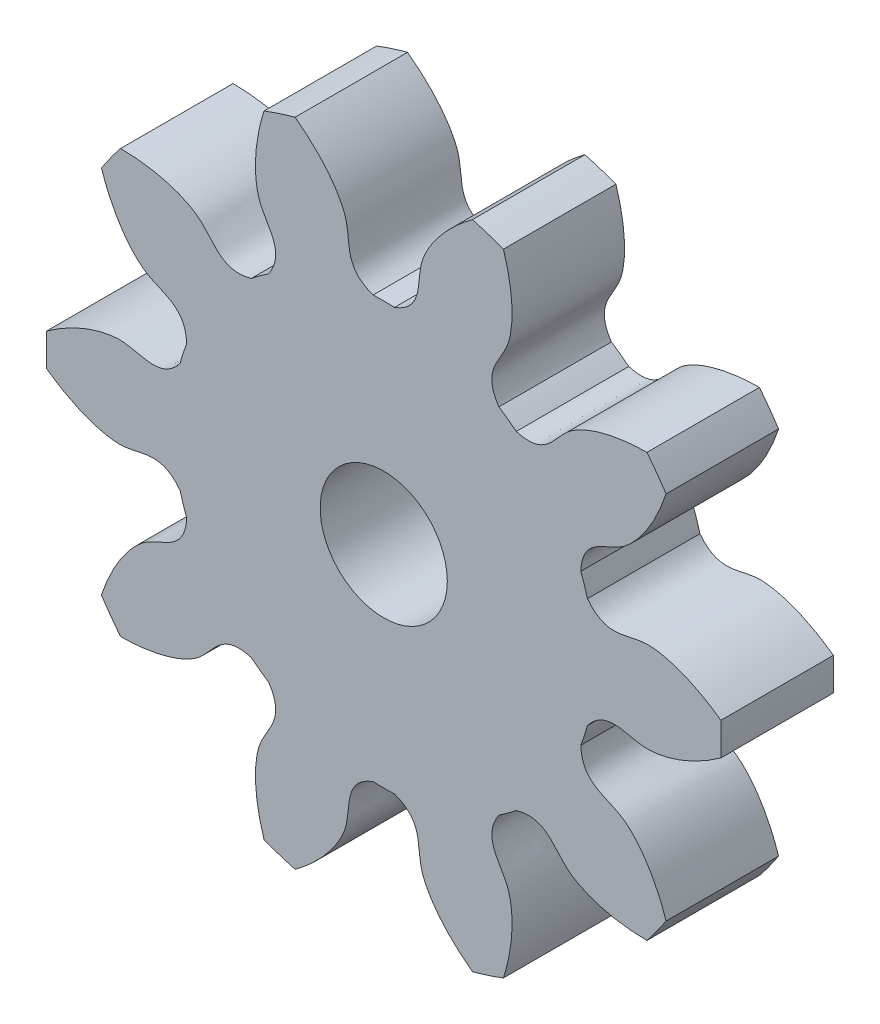
SolidWorks part; units mm, degrees
material "尼龙 6/10"
ref_plane "前视基准面" through (0, 0, 0) normal (0, 0, 1) x (1, 0, 0)
ref_plane "上视基准面" through (0, 0, 0) normal (0, 1, 0) x (1, 0, 0)
ref_plane "右视基准面" through (0, 0, 0) normal (1, 0, 0) x (0, 0, -1)
sketch "草图1" plane through (0, 0, 0) normal (0, 0, 1) x (1, 0, 0)
  circle A0 centre (0, 0) radius 3
extrude "凸台-拉伸1" add sketch "草图1" along normal blind 1
ref_axis "基准轴1" through (0, 0, -1.5) along (0, 0, 1)
sketch "草图2" plane through (0, 0, 0) normal (0, 0, 1) x (1, 0, 0)
  line L0 (0, 0) -> (0, 3) construction
  circle A0 centre (0, 0) radius 3 construction
  arc A1 (0.0952, 1.8726) -> (-0.0952, 1.8726) centre (0, 0) ccw
  arc A2 (2.1268, 3.3471) -> (-2.1268, 3.3471) centre (0, 0) ccw
  spline S0 degree 3 poles (0.0952, 1.8726) (0.3627, 1.9703) (0.2869, 2.1853) (0.3443, 2.3623) (0.3473, 2.3708) (0.3507, 2.38) (0.3546, 2.3901) (0.3591, 2.4009) (0.3642, 2.4126) (0.3699, 2.4249) (0.3763, 2.438) (0.3834, 2.4518) (0.3911, 2.4663) (0.3997, 2.4815) (0.409, 2.4972) (0.4191, 2.5136) (0.4301, 2.5306) (0.4419, 2.5481) (0.4546, 2.5662) (0.4682, 2.5848) (0.4828, 2.6038) (0.4983, 2.6233) (0.5148, 2.6432) (0.5323, 2.6634) (0.5509, 2.684) (0.5705, 2.7049) (0.5911, 2.7261) (0.6129, 2.7476) (0.6358, 2.7692) (0.6598, 2.791) (0.6849, 2.8129) (0.7112, 2.835) (0.7386, 2.8571) (0.7672, 2.8792) (0.7971, 2.9013) (0.8281, 2.9234) (0.8603, 2.9453) (0.8938, 2.9671) (0.9285, 2.9888) (0.9644, 3.0102) (1.0015, 3.0314) (1.0399, 3.0522) (1.0796, 3.0728) (1.1204, 3.0929) (1.1626, 3.1126) (1.2059, 3.1319) (1.2506, 3.1506) (1.2964, 3.1688) (1.3435, 3.1864) (1.3918, 3.2034) (1.4414, 3.2197) (1.4921, 3.2353) (1.5441, 3.2501) (1.5972, 3.2642) (1.6516, 3.2773) (1.7071, 3.2896) (1.7638, 3.301) (1.8216, 3.3114) (1.8805, 3.3208) (1.9405, 3.3291) (2.0227, 3.3388) (2.0849, 3.3443) (2.1268, 3.3471) knots 0 0 0 0 0.201721 0.204697 0.208023 0.211699 0.215726 0.220102 0.224829 0.229906 0.235332 0.241109 0.247237 0.253714 0.260541 0.267719 0.275246 0.283124 0.291352 0.29993 0.308858 0.318136 0.327765 0.337743 0.348072 0.358751 0.36978 0.381158 0.392888 0.404967 0.417396 0.430176 0.443305 0.456785 0.470615 0.484795 0.499325 0.514205 0.529435 0.545016 0.560946 0.577227 0.593858 0.610839 0.62817 0.645851 0.663882 0.682264 0.700995 0.720077 0.739509 0.759291 0.779423 0.799905 0.820737 0.84192 0.863452 0.885335 0.907568 0.930151 0.953084 1 1 1 1
  spline S1 degree 3 poles (-0.0952, 1.8726) (-0.3627, 1.9703) (-0.2869, 2.1853) (-0.3443, 2.3623) (-0.3473, 2.3708) (-0.3507, 2.38) (-0.3546, 2.3901) (-0.3591, 2.4009) (-0.3642, 2.4126) (-0.3699, 2.4249) (-0.3763, 2.438) (-0.3834, 2.4518) (-0.3911, 2.4663) (-0.3997, 2.4815) (-0.409, 2.4972) (-0.4191, 2.5136) (-0.4301, 2.5306) (-0.4419, 2.5481) (-0.4546, 2.5662) (-0.4682, 2.5848) (-0.4828, 2.6038) (-0.4983, 2.6233) (-0.5148, 2.6432) (-0.5323, 2.6634) (-0.5509, 2.684) (-0.5705, 2.7049) (-0.5911, 2.7261) (-0.6129, 2.7476) (-0.6358, 2.7692) (-0.6598, 2.791) (-0.6849, 2.8129) (-0.7112, 2.835) (-0.7386, 2.8571) (-0.7672, 2.8792) (-0.7971, 2.9013) (-0.8281, 2.9234) (-0.8603, 2.9453) (-0.8938, 2.9671) (-0.9285, 2.9888) (-0.9644, 3.0102) (-1.0015, 3.0314) (-1.0399, 3.0522) (-1.0796, 3.0728) (-1.1204, 3.0929) (-1.1626, 3.1126) (-1.2059, 3.1319) (-1.2506, 3.1506) (-1.2964, 3.1688) (-1.3435, 3.1864) (-1.3918, 3.2034) (-1.4414, 3.2197) (-1.4921, 3.2353) (-1.5441, 3.2501) (-1.5972, 3.2642) (-1.6516, 3.2773) (-1.7071, 3.2896) (-1.7638, 3.301) (-1.8216, 3.3114) (-1.8805, 3.3208) (-1.9405, 3.3291) (-2.0227, 3.3388) (-2.0849, 3.3443) (-2.1268, 3.3471) knots 0 0 0 0 0.201721 0.204697 0.208023 0.211699 0.215726 0.220102 0.224829 0.229906 0.235332 0.241109 0.247237 0.253714 0.260541 0.267719 0.275246 0.283124 0.291352 0.29993 0.308858 0.318136 0.327765 0.337743 0.348072 0.358751 0.36978 0.381158 0.392888 0.404967 0.417396 0.430176 0.443305 0.456785 0.470615 0.484795 0.499325 0.514205 0.529435 0.545016 0.560946 0.577227 0.593858 0.610839 0.62817 0.645851 0.663882 0.682264 0.700995 0.720077 0.739509 0.759291 0.779423 0.799905 0.820737 0.84192 0.863452 0.885335 0.907568 0.930151 0.953084 1 1 1 1
extrude "切除-拉伸1" cut sketch "草图2" along normal through all
pattern_circular "阵列(圆周)1" count 10 every 36 about axis through (0, 0, -1.5) along (0, 0, 1) of "切除-拉伸1"
sketch "草图3" [suppressed] plane through (0, 0, 0) normal (0, 0, 1) x (1, 0, 0)
  circle A0 centre (0, 0) radius 2.5 construction
  dimension "Dn" = 5
sketch "草图4" plane through (0, 0, 1) normal (0, 0, 1) x (1, 0, 0)
  circle A0 centre (0, 0) radius 0.565
  dimension "D1" = 1.13
extrude "切除-拉伸2" cut sketch "草图4" against normal blind 10
